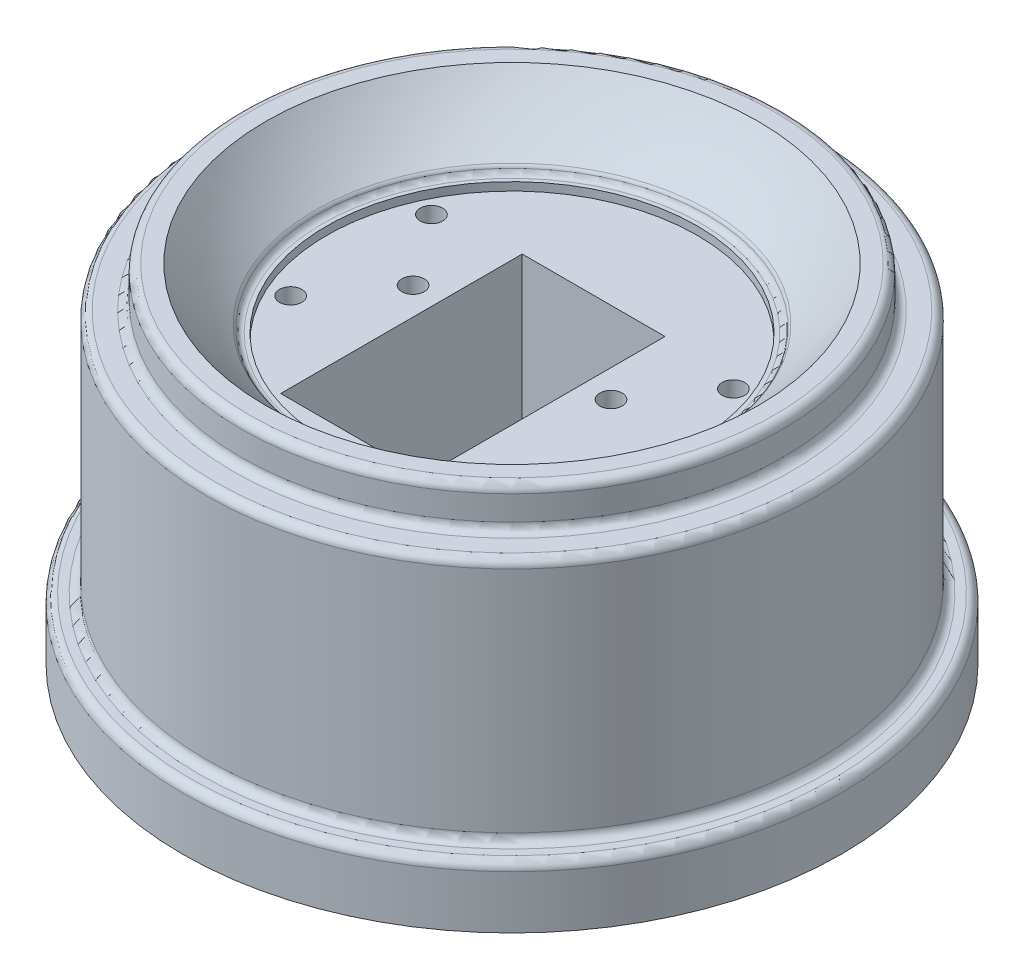
SolidWorks part; units mm, degrees
ref_plane "Front Plane" through (0, 0, 0) normal (0, 0, 1) x (1, 0, 0)
ref_plane "Top Plane" through (0, 0, 0) normal (0, 1, 0) x (1, 0, 0)
ref_plane "Right Plane" through (0, 0, 0) normal (1, 0, 0) x (0, 0, -1)
sketch "Sketch1" plane through (0, 0, 0) normal (0, 0, 1) x (1, 0, 0)
  line L0 (-46.4209, -58.8685) -> (46.4209, -58.8685) construction
  line L2 (60.3417, -44.1185) -> (66.3417, -44.1185)
  line L3 (58.3792, -44.1185) -> (-58.3792, -44.1185) construction
  line L4 (0, -129.1185) -> (0, -60.8685)
  line L5 (66.3417, -44.1185) -> (66.3417, -54.1185)
  line L6 (66.3417, -54.1185) -> (74.75, -54.1185)
  line L7 (74.75, -54.1185) -> (74.75, -114.1185)
  line L8 (74.75, -114.1185) -> (80.75, -114.1185)
  line L9 (80.75, -114.1185) -> (80.75, -129.1185)
  line L10 (80.75, -129.1185) -> (0, -129.1185)
  line L11 (-45.425, -60.8685) -> (45.425, -60.8685) construction
  line L12 (0, -60.8685) -> (45.425, -60.8685)
  line L13 (45.425, -60.8685) -> (45.425, -58.8685)
  line L15 (45.425, -58.8685) -> (46.4209, -58.8685)
  arc A0 (46.4209, -58.8685) -> (47.8684, -57.7617) centre (46.4209, -57.3685) ccw construction
  arc A1 (48.3458, -57.0109) -> (47.8684, -57.7617) centre (49.316, -58.1549) ccw construction
  arc A2 (48.3458, -57.0109) -> (-48.3458, -57.0109) centre (0, 0) ccw construction
  arc A3 (46.4209, -58.8685) -> (47.8684, -57.7617) centre (46.4209, -57.3685) ccw
  arc A4 (48.3458, -57.0109) -> (47.8684, -57.7617) centre (49.316, -58.1549) ccw
  arc A5 (48.3458, -57.0109) -> (60.3417, -44.1185) centre (0, 0) ccw
  point P17 (80.75, -121.6185)
  point P21 (74.75, 0)
  dimension "D1" = 6
  dimension "D2" = 10
  dimension "D3" = 6
  dimension "D4" = 15
  dimension "D5" = 85
revolve "Revolve1" add sketch "Sketch1" angle 360 about L4
fillet "Fillet1" radius 2 3 edges at (0, -114.1185, -80.75) (0, -54.1185, -74.75) (0, -44.1185, -66.3417)
fillet "Fillet2" radius 2 2 edges at (0, -114.1185, -74.75) (0, -54.1185, -66.3417)
sketch "Sketch2" plane through (0, -129.1185, 0) normal (0, -1, 0) x (1, 0, 0)
  line L0 (31, 15.8) -> (-31, 15.8)
  line L1 (-31, -47) -> (31, -47)
  line L2 (-31, -47) -> (-31, 47)
  line L3 (-31, 47) -> (31, 47)
  line L4 (31, -47) -> (31, 47)
  line L5 (-31, -47) -> (31, 47) construction
  line L6 (-31, 47) -> (31, -47) construction
  line L8 (-31, -47) -> (31, -47)
  line L9 (-31, -47) -> (-31, -15.8)
  line L10 (-31, -15.8) -> (31, -15.8)
  line L11 (31, -47) -> (31, -15.8)
  point P0 (0, 0)
  dimension "D1" = 94
  dimension "D2" = 62
  dimension "D3" = 31.2
  dimension "D4" = 31.2
extrude "Cut-Extrude1" cut sketch "Sketch2" against normal blind 33 contours L0 L4 L3 L2 region at (0, -129.1185, 31.4)
sketch "Sketch3" plane through (0, -129.1185, 0) normal (0, -1, 0) x (1, 0, 0)
  line L1 (43, 57) -> (-43, 57)
  line L2 (43, 57) -> (43, -57)
  line L3 (43, -57) -> (-43, -57)
  line L4 (-43, 57) -> (-43, -57)
  line L5 (43, 57) -> (-43, -57) construction
  line L6 (43, -57) -> (-43, 57) construction
  point P0 (0, 0)
  dimension "D1" = 114
  dimension "D2" = 86
extrude "Cut-Extrude2" cut sketch "Sketch3" against normal blind 3
fillet "Fillet3" radius 10 4 edges at (-43, -127.6185, 57) (-43, -127.6185, -57) (43, -127.6185, -57) (43, -127.6185, 57)
extrude "Cut-Extrude3" cut sketch "Sketch2<3>" against normal blind 16 from surface contours L10 L2 L1 L4 region at (0, -129.1185, -31.4) starting at face at (0, -126.1185, 31.4)
sketch "Sketch2<3>" plane through (0, -129.1185, 0) normal (0, -1, 0) x (1, 0, 0) same geometry as "Sketch2"
extrude "Cut-Extrude4" cut sketch "Sketch2<4>" against normal up to surface (33 mm away) contours L2 L10 L4 L0 region at (0, -129.1185, 0) up to face at (0, -96.1185, 31.4)
sketch "Sketch2<4>" plane through (0, -129.1185, 0) normal (0, -1, 0) x (1, 0, 0) same geometry as "Sketch2"
sketch "Sketch6" plane through (0, -96.1185, 0) normal (0, -1, 0) x (-1, 0, 0)
  line L1 (17.5, 20) -> (-17.5, 20)
  line L2 (17.5, 20) -> (17.5, -39.2)
  line L3 (17.5, -39.2) -> (-17.5, -39.2)
  line L4 (-17.5, 20) -> (-17.5, -39.2)
  line L5 (0, 0) -> (0, 20) construction
  dimension "D1" = 39.2
  dimension "D2" = 35
  dimension "D3" = 20
extrude "Cut-Extrude5" cut sketch "Sketch6" against normal up to next and the other way up to next
sketch "Sketch8" plane through (0, -129.1185, 0) normal (0, -1, 0) x (1, 0, 0)
  line L0 (0, 0) -> (0, -58.5739) construction
  line L1 (-24.25, 0) -> (24.25, 0) construction
  line L2 (0, 0) -> (37, 17.2534) construction
  line L3 (0, 0) -> (37, -17.2534) construction
  line L4 (0, 0) -> (-37, -17.2534) construction
  line L5 (0, 0) -> (-37, 17.2534) construction
  line L6 (31, -47) -> (31, 47) construction
  line L7 (31, -47) -> (31, 47) construction
  line L8 (43, 0) -> (31, 0) construction
  line L9 (43, -47) -> (43, 47) construction
  line L10 (17.5, -15.8) -> (17.5, 39.2) construction
  line L11 (17.5, -15.8) -> (17.5, 39.2) construction
  line L12 (31, 0) -> (17.5, 0) construction
  circle A0 centre (0, 0) radius 46.4209 construction
  circle A3 centre (0, 0) radius 46.4209 construction
  point P18 (37, 0)
  point P21 (24.25, 0)
  dimension "D1" = 65
hole_wizard "CBORE for M5 Hex Socket Head Cap Screw" positions "Sketch14" profile "Sketch15" counterbore size "M5" standard "ISO"
sketch "Sketch14" plane through (0, -126.1185, 0) normal (0, -1, 0) x (-1, 0, 0)
  point P0 (-37, -17.2534)
  point P2 (-37, 17.2534)
  point P4 (37, -17.2534)
  point P6 (37, 17.2534)
sketch "Sketch15" plane through (37, -126.1185, 17.2534) normal (1, 0, 0) x (0, 0, -1)
  line L0 (0, 0) -> (0, 81.6524)
  line L1 (0, 81.6524) -> (2.75, 80)
  line L2 (2.75, 80) -> (2.75, 5.4)
  line L3 (2.75, 5.4) -> (5, 5.4)
  line L4 (5, 5.4) -> (5, 0)
  line L5 (5, 0) -> (0, 0)
  line L6 (0, 81.6524) -> (-2.75, 80) construction
  line L7 (0, -6.35) -> (0, 107.95) construction
  dimension "Hole Dia." = 5.5
  dimension "Hole Depth" = 80
  dimension "C'Bore Dia." = 10
  dimension "C'Bore Depth" = 5.4
  dimension "Drill Angle" = 118
hole_wizard "CBORE for M5 Hex Socket Head Cap Screw6" positions "Sketch16" profile "Sketch17" counterbore size "M5" standard "ISO"
sketch "Sketch16" plane through (0, -96.1185, 0) normal (0, -1, 0) x (-1, 0, 0)
  point P0 (-24.25, 0)
  point P2 (24.25, 0)
sketch "Sketch17" plane through (24.25, -96.1185, 0) normal (1, 0, 0) x (0, 0, -1)
  line L0 (0, 0) -> (0, 51.6524)
  line L1 (0, 51.6524) -> (2.75, 50)
  line L2 (2.75, 50) -> (2.75, 5.4)
  line L3 (2.75, 5.4) -> (5, 5.4)
  line L4 (5, 5.4) -> (5, 0)
  line L5 (5, 0) -> (0, 0)
  line L6 (0, 51.6524) -> (-2.75, 50) construction
  line L7 (0, -6.35) -> (0, 107.95) construction
  dimension "Hole Dia." = 5.5
  dimension "Hole Depth" = 50
  dimension "C'Bore Dia." = 10
  dimension "C'Bore Depth" = 5.4
  dimension "Drill Angle" = 118
hole_wizard "M3 Tapped Hole1" positions "Sketch20" profile "Sketch21" tap size "M3" standard "ISO"
sketch "Sketch20" plane through (0, -126.1185, 0) normal (0, -1, 0) x (-1, 0, 0)
  point P0 (37, 37)
  point P3 (37, -37)
  point P6 (-37, -37)
  point P9 (-37, 37)
sketch "Sketch21" plane through (-37, -126.1185, -37) normal (1, 0, 0) x (0, 0, -1)
  line L0 (0, 0) -> (0, 20.7511)
  line L1 (0, 20.7511) -> (1.25, 20)
  line L2 (1.25, 20) -> (1.25, 0)
  line L5 (1.25, 0) -> (0, 0)
  line L10 (0, 20.7511) -> (-1.25, 20) construction
  line L11 (0, -6.35) -> (0, 107.95) construction
  dimension "Tap Drill Dia." = 2.5
  dimension "Tap Drill Depth" = 20
  dimension "Drill Angle" = 118
hole_wizard "M4 Tapped Hole1" positions "Sketch22" profile "Sketch24" tap size "M4" standard "ISO"
sketch "Sketch22" plane through (0, -96.1185, 0) normal (0, -1, 0) x (-1, 0, 0)
  point P0 (22.35, -31.4)
  point P3 (-22.35, -31.4)
sketch "Sketch24" plane through (-22.35, -96.1185, 31.4) normal (1, 0, 0) x (0, 0, -1)
  line L0 (0, 0) -> (0, 10.9914)
  line L1 (0, 10.9914) -> (1.65, 10)
  line L2 (1.65, 10) -> (1.65, 0)
  line L5 (1.65, 0) -> (0, 0)
  line L10 (0, 10.9914) -> (-1.65, 10) construction
  line L11 (0, -6.35) -> (0, 107.95) construction
  dimension "Tap Drill Dia." = 3.3
  dimension "Tap Drill Depth" = 10
  dimension "Drill Angle" = 118
hole_wizard "M3 Tapped Hole2" positions "Sketch25" profile "Sketch26" tap size "M3" standard "ISO"
sketch "Sketch25" plane through (0, -111.1185, 0) normal (0, -1, 0) x (-1, 0, 0)
  point P0 (7.2, 31.4)
  point P3 (0, 31.4)
  point P6 (-7.2, 31.4)
sketch "Sketch26" plane through (-7.2, -111.1185, -31.4) normal (1, 0, 0) x (0, 0, -1)
  line L0 (0, 0) -> (0, 16.7511)
  line L1 (0, 16.7511) -> (1.25, 16)
  line L2 (1.25, 16) -> (1.25, 1.75)
  line L3 (1.25, 1.75) -> (3, 0)
  line L4 (3, 0) -> (0, 0)
  line L5 (-1.25, 1.75) -> (-3, 0) construction
  line L6 (0, 16.7511) -> (-1.25, 16) construction
  line L7 (0, -6.35) -> (0, 107.95) construction
  dimension "Tap Drill Dia." = 2.5
  dimension "Tap Drill Depth" = 16
  dimension "Near C'Sink Dia." = 6
  dimension "Near C'Sink Angle" = 90
  dimension "Drill Angle" = 118
